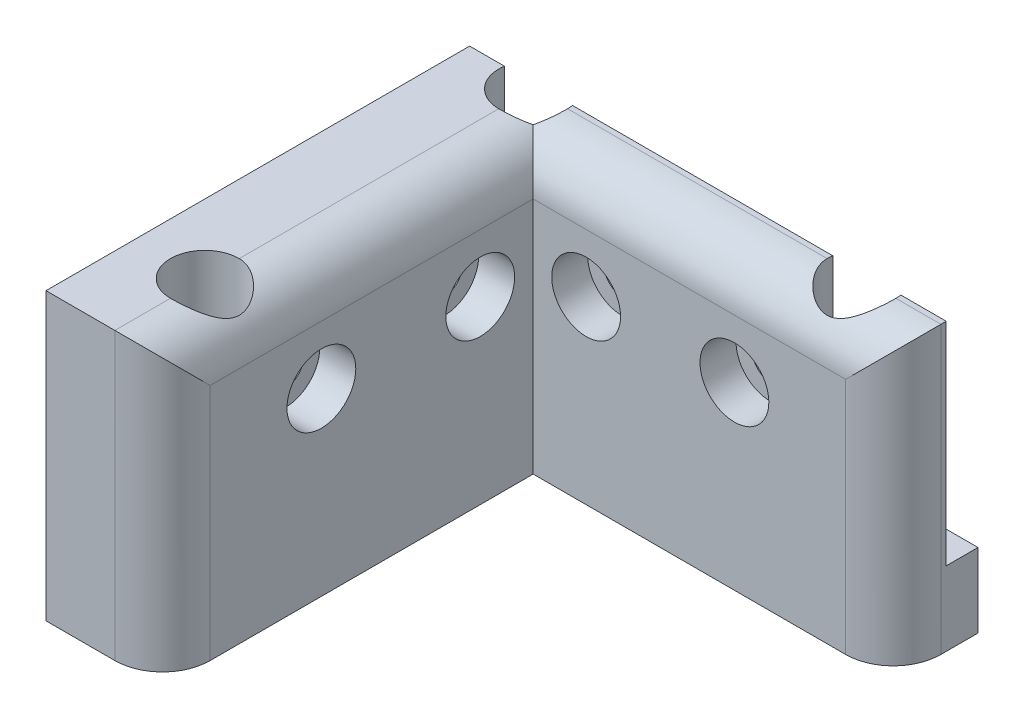
SolidWorks part; units mm, degrees
material "ABS"
ref_plane "Front Plane" through (0, 0, 0) normal (0, 0, 1) x (1, 0, 0)
ref_plane "Top Plane" through (0, 0, 0) normal (0, 1, 0) x (1, 0, 0)
ref_plane "Right Plane" through (0, 0, 0) normal (1, 0, 0) x (0, 0, -1)
sketch "Sketch1" plane through (0, 0, 0) normal (0, 1, 0) x (1, 0, 0)
  line L1 (0, 0) -> (45, 0)
  line L2 (0, 0) -> (0, 40)
  line L3 (0, 40) -> (45, 40)
  line L4 (45, 0) -> (45, 40)
  dimension "D1" = 45
  dimension "D2" = 40
extrude "Boss-Extrude1" add sketch "Sketch1" along normal blind 29
sketch "Sketch33" plane through (0, 29, 0) normal (0, 1, 0) x (1, 0, 0)
  line L0 (0, 40) -> (0, 0) construction
  line L1 (45, 0) -> (11, 0)
  line L2 (45, 0) -> (45, 35)
  line L3 (45, 35) -> (11, 35)
  line L4 (11, 0) -> (11, 35)
  line L5 (45, 40) -> (0, 40) construction
  dimension "D1" = 11
  dimension "D2" = 5
extrude "Cut-Extrude7" cut sketch "Sketch33" against normal through all
sketch "Sketch39" plane through (0, 0, -40) normal (0, 0, -1) x (-1, 0, 0)
  line L0 (0, 29) -> (0, 0) construction
  line L1 (-45, 0) -> (0, 0)
  line L2 (-45, 0) -> (-45, 9)
  line L3 (-45, 9) -> (0, 9)
  line L4 (0, 0) -> (0, 9)
  dimension "D1" = 9
extrude "Boss-Extrude2" add sketch "Sketch39" along normal blind 3
sketch "Sketch21" plane through (0, 29, 0) normal (0, 1, 0) x (1, 0, 0)
  line L0 (45, 40) -> (0, 40) construction
  circle A1 centre (6.5, 39.5) radius 1.75
  circle A2 centre (6.5, 8.5) radius 1.75
  circle A3 centre (37.5, 39.5) radius 1.75
  dimension "D3" = 0.5
  dimension "D4" = 3.5
  dimension "D7" = 3.5
  dimension "D8" = 3.5
  dimension "D1" = 0.5
  dimension "D2" = 31
extrude "Cut-Extrude6" cut sketch "Sketch21" against normal through all both and the other way through all
sketch "Sketch34" plane through (0, 29, 0) normal (0, 1, 0) x (1, 0, 0)
  circle A0 centre (6.5, 8.5) radius 3.25
  circle A1 centre (6.5, 39.5) radius 3.25
  circle A2 centre (37.5, 39.5) radius 3.25
  dimension "D1" = 6.5
  dimension "D2" = 6.5
  dimension "D3" = 6.5
extrude "Cut-Extrude8" cut sketch "Sketch34" against normal blind 23
hole_wizard "CBORE for M3 Hex Socket Head Cap Screw1" positions "Sketch35" profile "Sketch36" counterbore size "M3" standard "ISO" end condition through all
sketch "Sketch35" plane through (11, 0, 0) normal (1, 0, 0) x (0, 0, -1)
  line L1 (0, 0) -> (0, 29) construction
  line L2 (35, 0) -> (35, 29) construction
  line L3 (35, 29) -> (0, 29) construction
  point P0 (15, 19)
  point P2 (30, 19)
  dimension "D1" = 10
  dimension "D2" = 10
  dimension "D3" = 15
  dimension "D4" = 5
sketch "Sketch36" plane through (11, 19, -15) normal (0, 1, 0) x (0, 0, -1)
  line L0 (0, 0) -> (0, 11)
  line L1 (0, 11) -> (1.7, 11)
  line L3 (1.7, 11) -> (1.7, 3.4)
  line L4 (1.7, 3.4) -> (3.25, 3.4)
  line L5 (3.25, 3.4) -> (3.25, 0)
  line L7 (3.25, 0) -> (0, 0)
  line L11 (0, -6.35) -> (0, 107.95) construction
  dimension "Thru Hole Dia." = 3.4
  dimension "Thru Hole Depth" = 11
  dimension "C'Bore Dia." = 6.5
  dimension "C'Bore Depth" = 3.4
hole_wizard "CBORE for M3 Hex Socket Head Cap Screw2" positions "Sketch37" profile "Sketch38" counterbore size "M3" standard "ISO" end condition through all
sketch "Sketch37" plane through (0, 0, -35) normal (0, 0, 1) x (1, 0, 0)
  line L1 (11, 0) -> (11, 29) construction
  line L2 (45, 0) -> (45, 29) construction
  line L3 (45, 29) -> (11, 29) construction
  point P0 (16, 19)
  point P2 (30, 19)
  dimension "D1" = 10
  dimension "D2" = 10
  dimension "D3" = 5
  dimension "D4" = 15
sketch "Sketch38" plane through (16, 19, -35) normal (1, 0, 0) x (0, -1, 0)
  line L0 (0, 0) -> (0, 8)
  line L1 (0, 8) -> (1.7, 8)
  line L3 (1.7, 8) -> (1.7, 3.4)
  line L4 (1.7, 3.4) -> (3.25, 3.4)
  line L5 (3.25, 3.4) -> (3.25, 0)
  line L7 (3.25, 0) -> (0, 0)
  line L11 (0, -6.35) -> (0, 107.95) construction
  dimension "Thru Hole Dia." = 3.4
  dimension "Thru Hole Depth" = 8
  dimension "C'Bore Dia." = 6.5
  dimension "C'Bore Depth" = 3.4
fillet "Fillet1" radius 4.5 4 edges at (11, 14.5, 0) (45, 14.5, -35) (28, 29, -35) (11, 29, -17.5)
sketch "Sketch40" plane through (0, 0, 0) normal (-1, 0, 0) x (0, 0, 1)
  line L0 (-43, 0) -> (-43, 9) construction
  line L1 (-43, 2) -> (0, 2)
  line L2 (-43, 2) -> (-43, 0)
  line L3 (-43, 0) -> (0, 0)
  line L4 (0, 2) -> (0, 0)
  dimension "D1" = 2
extrude "Cut-Extrude9" cut sketch "Sketch40" against normal through all
mirror "Mirror1" [suppressed] of bodies 125 122
delete or keep bodies "Body-Delete/Keep 1" [suppressed] type delete bodies bodies 125
